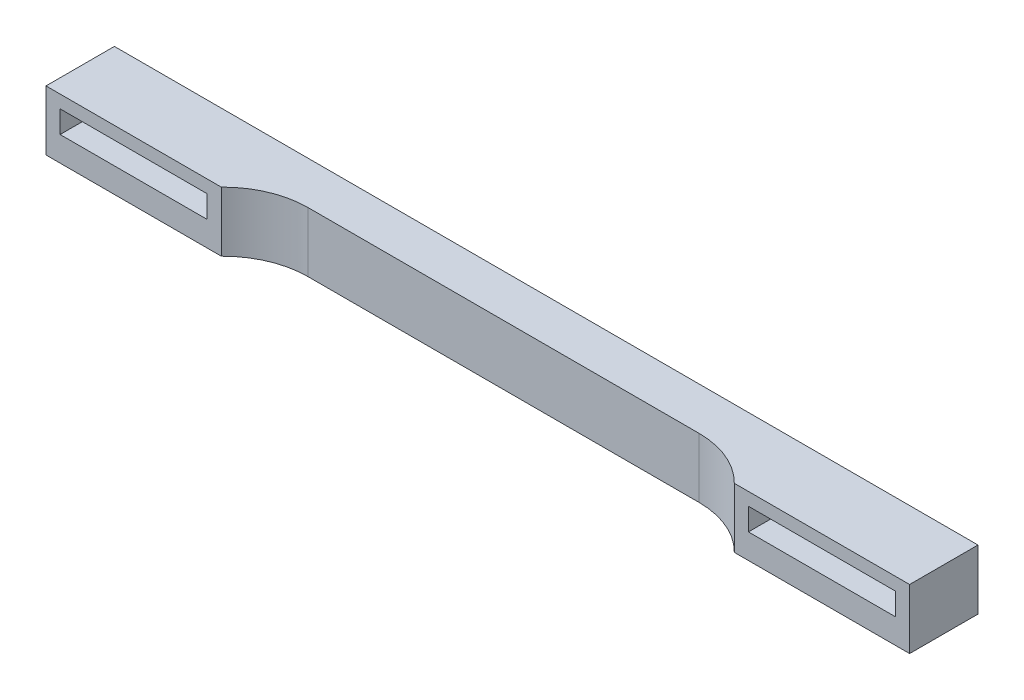
SolidWorks part; units mm, degrees
ref_plane "Front Plane" through (0, 0, 0) normal (0, 0, 1) x (1, 0, 0)
ref_plane "Top Plane" through (0, 0, 0) normal (0, 1, 0) x (1, 0, 0)
ref_plane "Right Plane" through (0, 0, 0) normal (1, 0, 0) x (0, 0, -1)
sketch "Sketch2" plane through (0, 0, 0) normal (0, 1, 0) x (1, 0, 0)
  line L0 (30, 0) -> (-30, 0)
  line L1 (-30, 0) -> (-30, 5)
  line L2 (-30, 5) -> (30, 5)
  line L3 (30, 5) -> (30, 0)
  line L4 (-30, 0) -> (-30, -3)
  line L5 (-30, -3) -> (-50.5, -3)
  line L6 (-50.5, -3) -> (-50.5, 5)
  line L7 (-50.5, 5) -> (-30, 5)
  line L8 (30, 5) -> (50.5, 5)
  line L9 (50.5, 5) -> (50.5, -3)
  line L10 (50.5, -3) -> (30, -3)
  line L11 (30, -3) -> (30, 0)
  point P4 (0, 0)
  dimension "D1" = 60
  dimension "D2" = 5
  dimension "D3" = 20.5
  dimension "D4" = 8
  dimension "D5" = 8
  dimension "D6" = 20.5
extrude "Boss-Extrude1" add sketch "Sketch2" along normal blind 7 contours L7 L6 L5 L4 L1 | L3 L2 L1 L0 | L11 L10 L9 L8 L3 region at (0, 0, -2.5) region at (40.25, 0, -1) region at (-40.25, 0, -1)
sketch "Sketch4" plane through (0, 0, 3) normal (0, 0, 1) x (1, 0, 0)
  line L0 (-40.25, 7) -> (-40.25, 5.5)
  line L1 (-30, 7) -> (-50.5, 7) construction
  line L2 (-40.25, 5.5) -> (-48.85, 5.5)
  line L3 (-48.85, 5.5) -> (-48.85, 2.9)
  line L4 (-48.85, 2.9) -> (-31.65, 2.9)
  line L5 (-31.65, 2.9) -> (-31.65, 5.5)
  line L6 (-31.65, 5.5) -> (-40.25, 5.5)
  line L7 (0, 0) -> (0, 7)
  line L8 (30, 0) -> (-30, 0) construction
  line L9 (30, 7) -> (-30, 7) construction
  line L10 (48.85, 5.5) -> (48.85, 2.9)
  line L11 (40.25, 5.5) -> (48.85, 5.5)
  line L12 (31.65, 5.5) -> (40.25, 5.5)
  line L13 (31.65, 2.9) -> (31.65, 5.5)
  line L14 (48.85, 2.9) -> (31.65, 2.9)
  dimension "D1" = 1.5
  dimension "D2" = 8.6
  dimension "D3" = 8.6
  dimension "D4" = 2.6
extrude "Cut-Extrude1" cut sketch "Sketch4" against normal blind 12 contours L5 L6 L2 L3 L4 | L14 L10 L11 L12 L13 region at (-40.25, 4.2, 3) region at (40.25, 4.2, 3)
sketch "Sketch5" plane through (0, 0, 0) normal (0, -1, 0) x (1, 0, 0)
  line L0 (-40.25, 3) -> (-40.25, -1)
  line L1 (-30, 3) -> (-50.5, 3) construction
  line L2 (0, 0) -> (0, -5)
  line L3 (30, 0) -> (-30, 0) construction
  line L4 (-50.5, -5) -> (50.5, -5) construction
  circle A0 centre (-40.25, -1) radius 1.4
  circle A1 centre (40.25, -1) radius 1.4
  dimension "D1" = 4
  dimension "D2" = 2.8
extrude "Cut-Extrude2" cut sketch "Sketch5" against normal blind 3 contours A1 | A0 region at (40.25, 0, -1)
fillet "Fillet1" radius 10 2 edges at (-30, 3.5, 0) (30, 3.5, 0)
fillet "Fillet2" radius 0.3 2 edges at (40.25, 0, -2.4) (-40.25, 0, -2.4)
